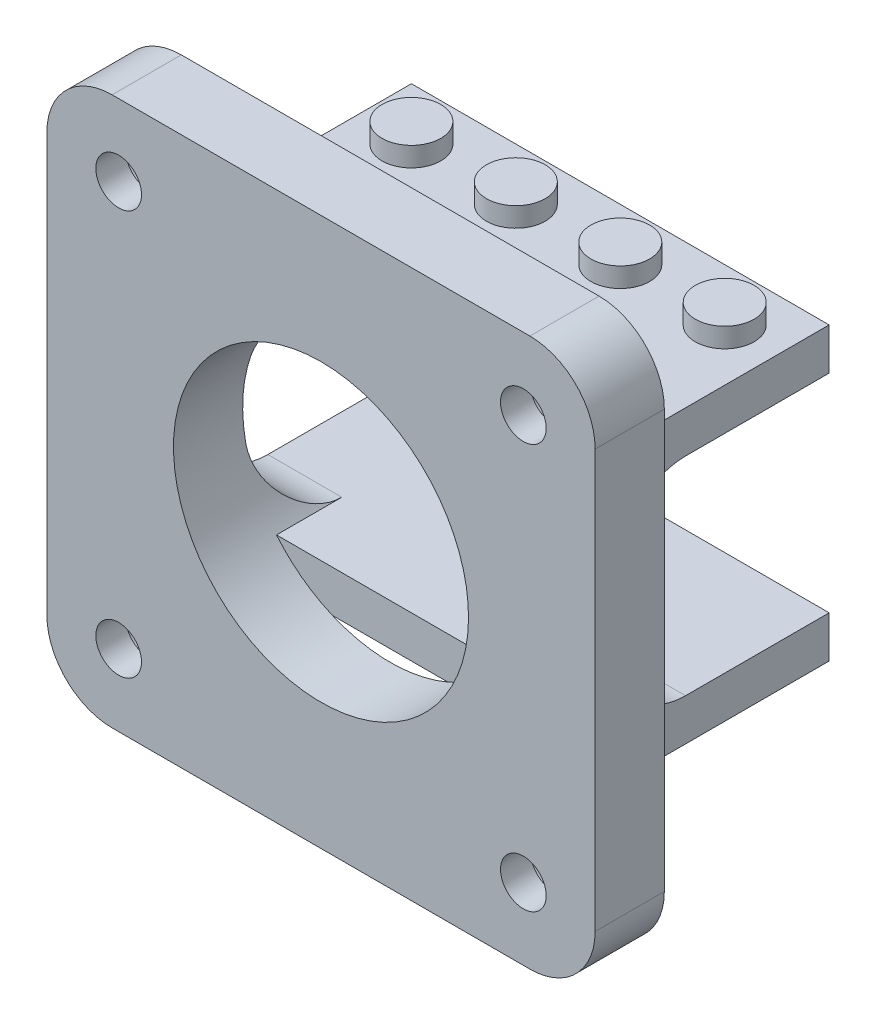
SolidWorks part; units mm, degrees
ref_plane "Front Plane" through (0, 0, 0) normal (0, 0, 1) x (1, 0, 0)
ref_plane "Top Plane" through (0, 0, 0) normal (0, 1, 0) x (1, 0, 0)
ref_plane "Right Plane" through (0, 0, 0) normal (1, 0, 0) x (0, 0, -1)
sketch "Sketch1" plane through (0, 0, 483.2559) normal (0, 0, -1) x (-1, 0, 0)
  line L6 (-277.129, 25.9629) -> (-245.129, 25.9629)
  line L9 (-282.129, 30.9629) -> (-282.129, 62.9629)
  line L10 (-277.129, 67.9629) -> (-245.129, 67.9629)
  line L11 (-240.129, 30.9629) -> (-240.129, 62.9629)
  line L12 (-282.129, 25.9629) -> (-240.129, 67.9629) construction
  line L13 (-282.129, 67.9629) -> (-240.129, 25.9629) construction
  circle A0 centre (-261.129, 46.9629) radius 10.8 construction
  circle A2 centre (-276.629, 62.4629) radius 1.75
  circle A27 centre (-261.129, 46.9629) radius 10.8 construction
  circle A32 centre (-245.629, 62.4629) radius 1.75
  circle A33 centre (-245.629, 31.4629) radius 1.75
  circle A34 centre (-276.629, 31.4629) radius 1.75
  circle A35 centre (-276.629, 62.4629) radius 3
  circle A36 centre (-245.629, 62.4629) radius 3
  circle A37 centre (-245.629, 31.4629) radius 3
  circle A38 centre (-276.629, 31.4629) radius 3
  arc A39 (-277.129, 25.9629) -> (-282.129, 30.9629) centre (-277.129, 30.9629) cw
  arc A40 (-245.129, 25.9629) -> (-240.129, 30.9629) centre (-245.129, 30.9629) ccw
  arc A41 (-245.129, 67.9629) -> (-240.129, 62.9629) centre (-245.129, 62.9629) cw
  arc A42 (-282.129, 62.9629) -> (-277.129, 67.9629) centre (-277.129, 62.9629) cw
  circle A43 centre (-261.129, 46.9629) radius 11.3
  point P0 (-261.129, 46.9629)
  line M31 (-276.8005, 26.1629) -> (-245.4574, 26.1629)
  arc M32 (-245.4574, 26.1629) -> (-244.1846, 26.6901) centre (-245.4574, 27.9629) ccw
  line M33 (-244.1846, 26.6901) -> (-240.8562, 30.0185)
  arc M34 (-240.8562, 30.0185) -> (-240.329, 31.2913) centre (-242.129, 31.2913) ccw
  line M35 (-240.329, 31.2913) -> (-240.329, 62.6344)
  arc M36 (-240.329, 62.6344) -> (-240.8562, 63.9072) centre (-242.129, 62.6344) ccw
  line M37 (-240.8562, 63.9072) -> (-244.1846, 67.2357)
  arc M38 (-244.1846, 67.2357) -> (-245.4574, 67.7629) centre (-245.4574, 65.9629) ccw
  line M39 (-245.4574, 67.7629) -> (-276.8005, 67.7629)
  arc M40 (-276.8005, 67.7629) -> (-278.0733, 67.2357) centre (-276.8005, 65.9629) ccw
  line M41 (-278.0733, 67.2357) -> (-281.4018, 63.9072)
  arc M42 (-281.4018, 63.9072) -> (-281.929, 62.6344) centre (-280.129, 62.6344) ccw
  line M43 (-281.929, 62.6344) -> (-281.929, 31.2913)
  arc M44 (-281.929, 31.2913) -> (-281.4018, 30.0185) centre (-280.129, 31.2913) ccw
  line M45 (-281.4018, 30.0185) -> (-278.0733, 26.6901)
  arc M46 (-278.0733, 26.6901) -> (-276.8005, 26.1629) centre (-276.8005, 27.9629) ccw
  circle M47 centre (-261.129, 46.9629) radius 11.2
  dimension "D3" = 6
  dimension "D4" = 5
  dimension "D5" = 0.5
  dimension "D2" = 3.5
  dimension "D1" = 42
extrude "Boss-Extrude1" add sketch "Sketch1" along normal up to surface (5.3 mm away) contours M31 M46 M45 M44 M43 M42 M41 M40 M39 M38 M37 M36 M35 M34 M33 M32 | A38 A34 | A35 A2 | A38 A37 A36 A35 M46 M31 M32 M33 M34 M35 M36 M37 M38 M39 M40 M41 M42 M43 M44 M45 M47 | A36 A32 | A37 A33 region at (280.2445, 27.8473, 483.2559) region at (279.5441, 62.4629, 483.2559) region at (248.5441, 62.4629, 483.2559) region at (248.5441, 31.4629, 483.2559) region at (279.5441, 31.4629, 483.2559) region at (277.2642, 26.8434, 483.2559)
extrude "Cut-Extrude1" cut sketch "Sketch1<3>" against normal blind 3 from surface contours A38 A34 | A35 A2 | A36 A32 | A37 A33 starting at face at (247.379, 31.4629, 477.9559)
sketch "Sketch1<3>" plane through (0, 0, 483.2559) normal (0, 0, -1) x (-1, 0, 0) same geometry as "Sketch1"
sketch "Sketch2" plane through (0, 0, 477.9559) normal (0, 0, -1) x (-1, 0, 0)
  line L0 (-278.754, 58.8629) -> (-246.754, 58.8629)
  line L3 (-246.754, 58.8629) -> (-246.754, 55.6629)
  line L4 (-246.754, 55.6629) -> (-278.754, 55.6629)
  line L5 (-278.754, 55.6629) -> (-278.754, 58.8629)
  line L8 (-278.754, 39.7629) -> (-246.754, 39.7629)
  line L9 (-246.754, 39.7629) -> (-246.754, 36.5629)
  line L10 (-246.754, 36.5629) -> (-278.754, 36.5629)
  line L11 (-278.754, 39.7629) -> (-278.754, 36.5629)
  line L16 (-245.129, 67.9629) -> (-277.129, 67.9629) construction
  line L17 (-282.129, 62.9629) -> (-282.129, 30.9629) construction
  line L25 (-245.129, 25.9629) -> (-277.129, 25.9629) construction
  dimension "D1" = 9.1
  dimension "D2" = 3.2
  dimension "D3" = 10.6
  dimension "D4" = 32
  dimension "D5" = 3.375
extrude "Boss-Extrude2" add sketch "Sketch2" along normal blind 16 contours L4 L0 | L4 | L10 L8 | L10 L8 | L10 L8 region at (262.754, 57.2629, 477.9559) region at (262.754, 38.1629, 477.9559)
sketch "Sketch4" plane through (0, 58.8629, 0) normal (0, 1, 0) x (1, 0, 0)
  circle A44 centre (274.754, -465.9559) radius 2.4 construction
  circle A45 centre (274.754, -473.9559) radius 2.4 construction
  circle A46 centre (250.754, -473.9559) radius 2.4 construction
  circle A47 centre (258.754, -473.9559) radius 2.4 construction
  circle A48 centre (266.754, -473.9559) radius 2.4 construction
  circle A49 centre (266.754, -465.9559) radius 2.4 construction
  circle A50 centre (258.754, -465.9559) radius 2.4 construction
  circle A51 centre (250.754, -465.9559) radius 2.4 construction
  circle A52 centre (274.754, -465.9559) radius 2.4 construction
  circle A53 centre (274.754, -473.9559) radius 2.4 construction
  circle A54 centre (250.754, -473.9559) radius 2.4 construction
  circle A55 centre (258.754, -473.9559) radius 2.4 construction
  circle A56 centre (266.754, -473.9559) radius 2.4 construction
  circle A57 centre (266.754, -465.9559) radius 2.4 construction
  circle A58 centre (258.754, -465.9559) radius 2.4 construction
  circle A59 centre (250.754, -465.9559) radius 2.4 construction
  circle A60 centre (250.754, -465.9559) radius 2.55
  circle A61 centre (250.754, -465.9559) radius 2.25
  circle A62 centre (258.754, -465.9559) radius 2.55
  circle A63 centre (258.754, -465.9559) radius 2.25
  circle A64 centre (266.754, -465.9559) radius 2.55
  circle A65 centre (266.754, -465.9559) radius 2.25
  circle A66 centre (274.754, -465.9559) radius 2.55
  circle A67 centre (274.754, -465.9559) radius 2.25
  circle A68 centre (274.754, -473.9559) radius 2.55
  circle A69 centre (274.754, -473.9559) radius 2.25
  circle A70 centre (266.754, -473.9559) radius 2.55
  circle A71 centre (266.754, -473.9559) radius 2.25
  circle A72 centre (258.754, -473.9559) radius 2.55
  circle A73 centre (258.754, -473.9559) radius 2.25
  circle A74 centre (250.754, -473.9559) radius 2.55
  circle A75 centre (250.754, -473.9559) radius 2.25
  dimension "D1" = 0.15
  dimension "D2" = 0.15
extrude "Boss-Extrude3" add sketch "Sketch4" along normal blind 1.5 contours A75 | A61 | A63 | A73 | A71 | A65 | A67 region at (250.754, 58.8629, 465.9559) region at (258.754, 58.8629, 465.9559) region at (266.754, 58.8629, 465.9559) region at (274.754, 58.8629, 465.9559) region at (266.754, 58.8629, 473.9559) region at (258.754, 58.8629, 473.9559) region at (250.754, 58.8629, 473.9559)
fillet "Fillet2" radius 5 4 edges at (274.2961, 39.7629, 477.9559) (249.5869, 39.7629, 477.9559) (250.3359, 55.6629, 477.9559) (273.547, 55.6629, 477.9559)
extrude "Cut-Extrude3" cut sketch "Sketch4<5>" along normal blind 1.7 from surface contours A68 | A66 | A64 | A70 | A72 | A62 | A74 | A60 starting at face at (262.2123, 36.5629, 472.6225)
sketch "Sketch4<5>" plane through (0, 58.8629, 0) normal (0, 1, 0) x (1, 0, 0) same geometry as "Sketch4"
